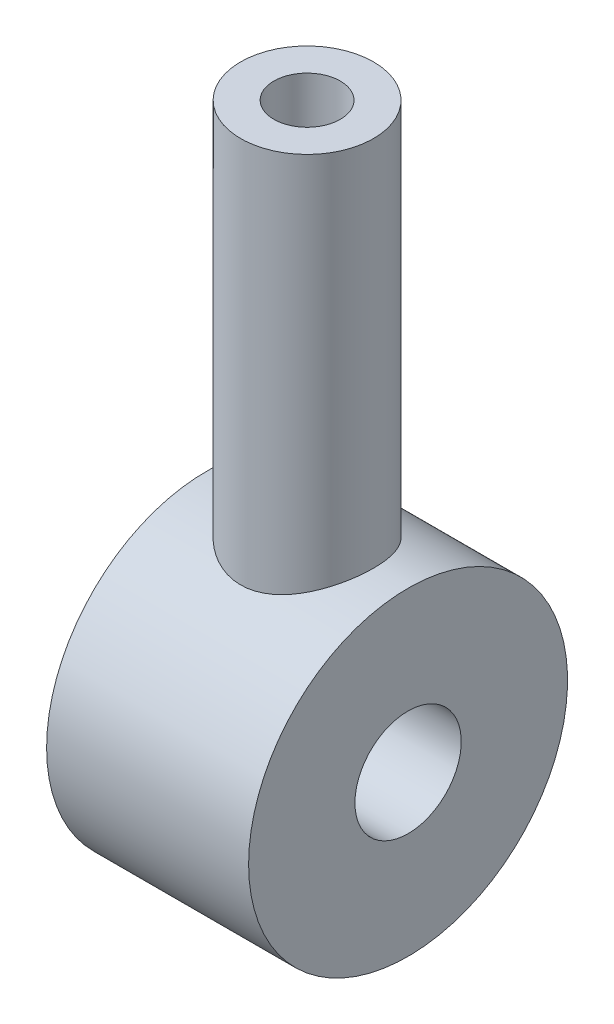
SolidWorks part; units mm, degrees
ref_plane "Front Plane" through (0, 0, 0) normal (0, 0, 1) x (1, 0, 0)
ref_plane "Top Plane" through (0, 0, 0) normal (0, 1, 0) x (1, 0, 0)
ref_plane "Right Plane" through (0, 0, 0) normal (1, 0, 0) x (0, 0, -1)
sketch "Eye Sketch" plane through (0, 0, 0) normal (0, 0, 1) x (1, 0, 0)
  line L0 (-3000, 0) -> (3000, 0) construction
  line L1 (-3.8, 2) -> (3.8, 2)
  line L2 (3.8, 2) -> (3.8, 6)
  line L3 (3.8, 6) -> (-3.8, 6)
  line L4 (-3.8, 6) -> (-3.8, 2)
revolve "Eye" add sketch "Eye Sketch" angle 360 about L0
ref_axis "Engine Axis" through (5.44, 0, 0) along (-1, 0, 0)
sketch "Shank Sketch" plane through (0, 0, 0) normal (0, 0, 1) x (1, 0, 0)
  line L0 (0, -5) -> (0, 40) construction
  line L1 (0, 5) -> (2.5, 5)
  line L2 (2.5, 5) -> (2.5, 20)
  line L3 (2.5, 20) -> (1.25, 20)
  line L4 (1.25, 20) -> (1.25, 10)
  line L5 (1.25, 10) -> (0, 10)
  line L6 (0, 10) -> (0, 5)
revolve "Shank" add sketch "Shank Sketch" angle 360 about L0
sketch "Ball Points" plane through (0, 0, 0) normal (0, 0, 1) x (1, 0, 0)
  point P0 (0, 0)
  point P1 (5, 0)
